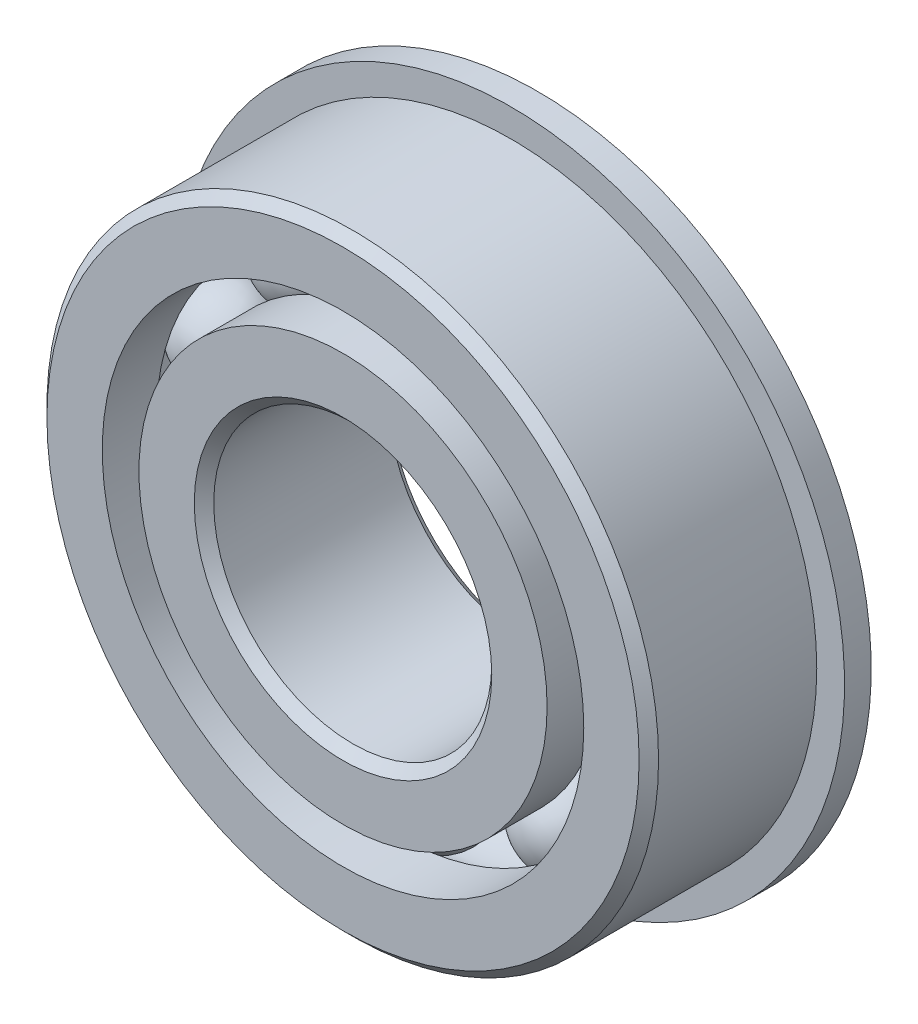
SolidWorks part; units mm, degrees
ref_plane "Front Plane" through (0, 0, 0) normal (0, 0, 1) x (1, 0, 0)
ref_plane "Top Plane" through (0, 0, 0) normal (0, 1, 0) x (1, 0, 0)
ref_plane "Right Plane" through (0, 0, 0) normal (1, 0, 0) x (0, 0, -1)
sketch "Sketch1" plane through (0, 0, 0) normal (1, 0, 0) x (0, 0, -1)
  line L0 (-5.5562, 0) -> (5.5562, 0) construction
  line L1 (0, 17.4625) -> (0, -17.4625) construction
  line L2 (5.0006, 17.4625) -> (-5.0006, 17.4625)
  line L3 (-5.0006, 17.4625) -> (-5.5563, 16.9069)
  line L4 (-5.5563, 16.9069) -> (-5.5563, 13.7467)
  line L5 (-5.5563, 13.7467) -> (-2.4694, 13.7467)
  line L6 (5.5563, 13.7467) -> (2.4694, 13.7467)
  line L7 (5.5563, 16.9069) -> (5.5563, 13.7467)
  line L8 (5.0006, 17.4625) -> (5.5563, 16.9069)
  line L9 (0, 17.4625) -> (0, 12.7) construction
  line L10 (0, 12.7) -> (0, 7.9375) construction
  arc A0 (-2.4694, 13.7467) -> (2.4694, 13.7467) centre (0, 12.7) cw
  point P14 (0, 7.9375)
  dimension "Width" = 11.1125
  dimension "OD" = 34.925
  dimension "D1" = 45
  dimension "D2" = 0.5556
  dimension "Shaft Dia" = 15.875
  dimension "D3" = 4.9389
  dimension "D4" = 1.0467
revolve "Revolve1" add sketch "Sketch1" angle 360 about L0
sketch "Sketch3" plane through (0, 0, 0) normal (1, 0, 0) x (0, 0, -1)
  line L0 (-5.5563, 11.6533) -> (-2.4694, 11.6533)
  line L1 (0, 17.4625) -> (0, -17.4625) construction
  line L2 (-5.5563, 16.9069) -> (-5.5563, 13.7467) construction
  line L3 (-5.5563, 11.6533) -> (-5.5562, 8.4931)
  line L4 (-5.0006, 17.4625) -> (-5.5563, 16.9069) construction
  line L5 (-5.5562, 8.4931) -> (-5.0006, 7.9375)
  line L6 (-5.0006, 7.9375) -> (5.0006, 7.9375)
  line L7 (5.0006, 17.4625) -> (5.0006, -17.4625) construction
  line L8 (5.0006, 7.9375) -> (5.5563, 8.4931)
  line L9 (5.5563, -16.9069) -> (5.5563, 16.9069) construction
  line L10 (5.5563, 8.4931) -> (5.5563, 11.6533)
  line L11 (5.5563, 11.6533) -> (2.4694, 11.6533)
  line L13 (5.0006, 17.4625) -> (5.5563, 16.9069) construction
  arc A0 (2.4694, 13.7467) -> (-2.4694, 13.7467) centre (0, 12.7) ccw construction
  arc A1 (2.4694, 11.6533) -> (-2.4694, 11.6533) centre (0, 12.7) cw
revolve "Revolve3" add sketch "Sketch3" angle 360 about L0
sketch "Sketch4" plane through (0, 0, 0) normal (1, 0, 0) x (0, 0, -1)
  line L0 (-2.6821, 12.7) -> (2.6821, 12.7)
  arc A2 (-2.6821, 12.7) -> (2.6821, 12.7) centre (0, 12.7) cw
  arc A3 (2.4694, 13.7467) -> (-2.4694, 13.7467) centre (0, 12.7) ccw construction
revolve "Revolve4" add sketch "Sketch4" angle 360 about L0
ref_axis "Axis1" through (0, 0, -5.5562) along (0, 0, 1)
pattern_circular "CirPattern1" count 10 every 36 about axis through (0, 0, -5.5562) along (0, 0, 1) of bodies 104
sketch "Sketch6" plane through (0, 0, 0) normal (1, 0, 0) x (0, 0, -1)
  line L0 (5.5562, 0) -> (-5.5562, 0) construction
  line L1 (5.5563, 13.7467) -> (4.0322, 13.7467)
  line L2 (5.5563, 13.7467) -> (5.5562, 19.05)
  line L3 (5.5562, 19.05) -> (4.0322, 19.05)
  line L4 (4.0322, 13.7467) -> (4.0322, 19.05)
  dimension "Th" = 1.524
  dimension "Flange OD" = 38.1
revolve "Revolve6" add sketch "Sketch6" angle 360 about L0
equation "\"D2@Sketch1\" = \"Width@Sketch1\"*.05"
equation "\"D3@Sketch1\" = \"Width@Sketch1\"/2.25"
equation "\"D4@Sketch1\" = (((\"OD@Sketch1\"-\"Width@Sketch1\")/2)/3.25)/3.5"
equation "\"D2@CirPattern1\" = 360/\"Balls@CirPattern1\""
